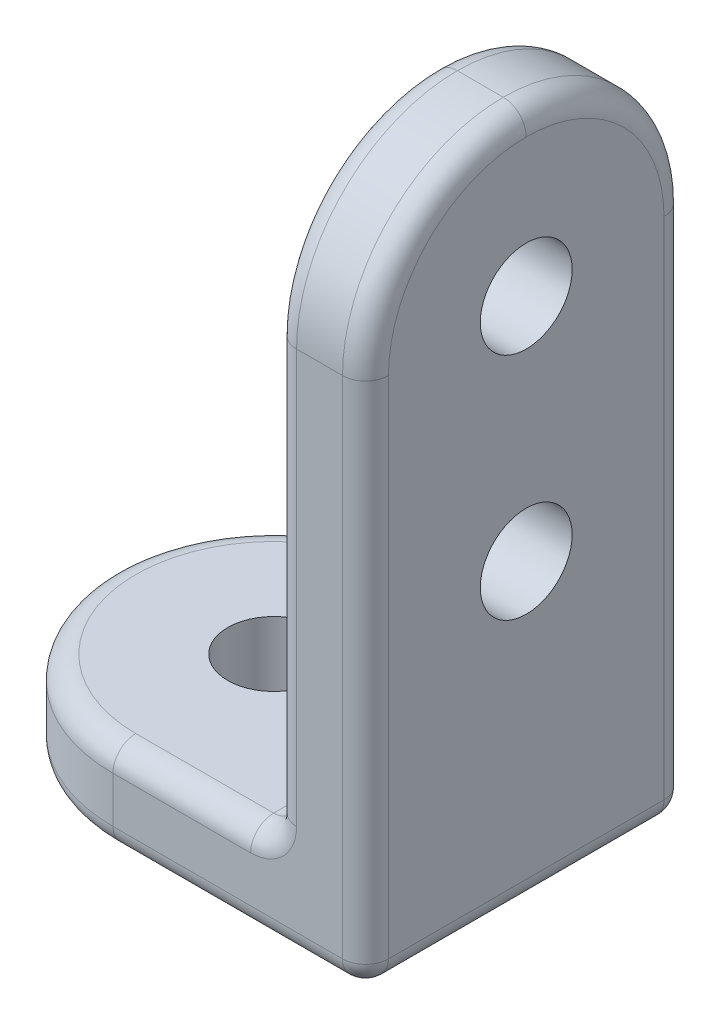
SolidWorks part; units mm, degrees
ref_plane "Front Plane" through (0, 0, 0) normal (0, 0, 1) x (1, 0, 0)
ref_plane "Top Plane" through (0, 0, 0) normal (0, 1, 0) x (1, 0, 0)
ref_plane "Right Plane" through (0, 0, 0) normal (1, 0, 0) x (0, 0, -1)
sketch "Sketch1" plane through (0, 0, 0) normal (0, 1, 0) x (1, 0, 0)
  line L0 (0, 7) -> (11, 7)
  line L1 (11, 7) -> (11, -7)
  line L2 (11, -7) -> (0, -7)
  circle A0 centre (0, 0) radius 2
  circle A1 centre (0, 0) radius 7
  dimension "D1" = 4
  dimension "D2" = 5
  dimension "D3" = 11
extrude "Boss-Extrude1" add sketch "Sketch1" along normal blind 4 contours A1 A0 | A1 L2 L1 L0 region at (8.0271, 0, 0) region at (4.8097, 0, -4.8097)
sketch "Sketch2" plane through (0, 4, 0) normal (0, 1, 0) x (1, 0, 0)
  line L0 (0, 7) -> (11, 7) construction
  line L1 (11, -7) -> (7, -7)
  line L2 (11, -7) -> (11, 7)
  line L3 (11, 7) -> (7, 7)
  line L4 (7, -7) -> (7, 7)
  dimension "D1" = 4
extrude "Boss-Extrude2" add sketch "Sketch2" along normal blind 26
sketch "Sketch4" plane through (7, 0, 0) normal (-1, 0, 0) x (0, 0, 1)
  line L0 (-7, 30) -> (7, 30) construction
  circle A0 centre (0, 23) radius 2
  circle A1 centre (0, 13) radius 2
  point P6 (0, 30)
  point P7 (0, 0)
  point P8 (0, 0)
  dimension "D1" = 4
  dimension "D2" = 4
  dimension "D3" = 10
  dimension "D4" = 7
extrude "Cut-Extrude2" cut sketch "Sketch4" against normal up to next
fillet "Fillet6" radius 7 2 edges at (9, 30, -7) (9, 30, 7)
fillet "Fillet7" radius 1 2 edges at (11, 0, 0) (7, 4, 0)
fillet "Fillet8" radius 1 18 edges at (7, 27.9497, 4.9497) (7, 27.9497, -4.9497) (7, 14, -7) (6.7071, 4.2929, -7) (3, 4, -7) (-7, 4, 0) (11, 27.9497, 4.9497) (11, 27.9497, -4.9497) (11, 12, -7) (10.7071, 0.2929, -7) (5, 0, -7) (-7, 0, 0) (3, 4, 7) (6.7071, 4.2929, 7) (7, 14, 7) (11, 12, 7) (10.7071, 0.2929, 7) (5, 0, 7)
